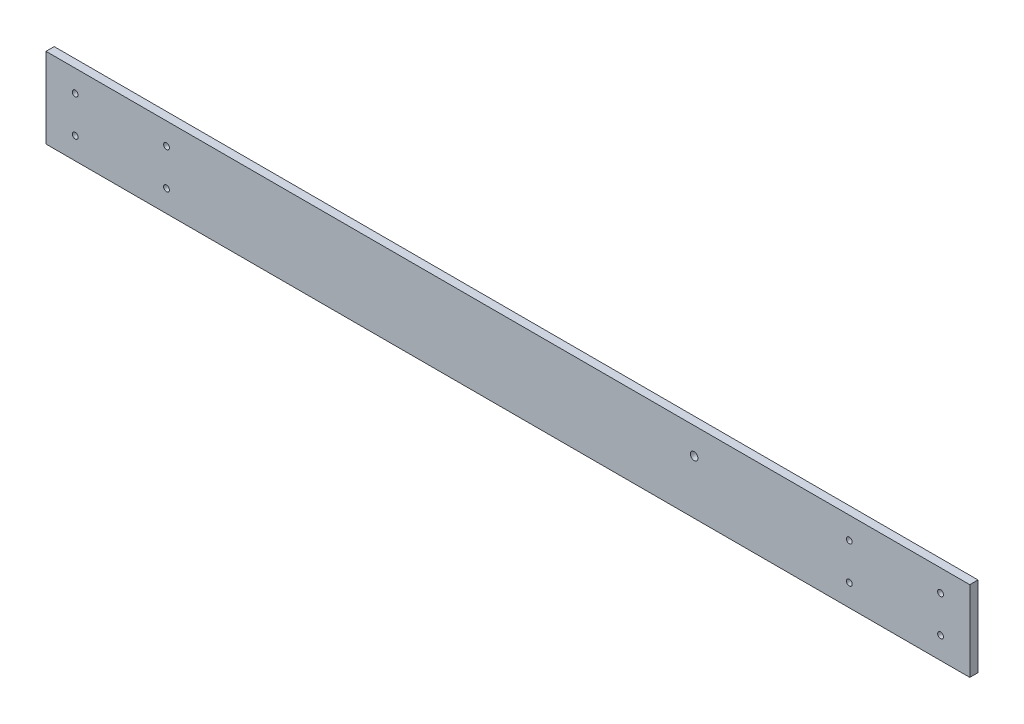
SolidWorks part; units mm, degrees
ref_plane "Front Plane" through (0, 0, 0) normal (0, 0, 1) x (1, 0, 0)
ref_plane "Top Plane" through (0, 0, 0) normal (0, 1, 0) x (1, 0, 0)
ref_plane "Right Plane" through (0, 0, 0) normal (1, 0, 0) x (0, 0, -1)
sketch "Sketch2" plane through (0, 0, 0) normal (0, 0, 1) x (1, 0, 0)
  line L0 (253, 0) -> (127, 0) construction
  line L1 (-253, -22) -> (253, -22)
  line L2 (-253, -22) -> (-253, 22)
  line L3 (-253, 22) -> (253, 22)
  line L4 (253, -22) -> (253, 22)
  line L5 (-253, -22) -> (253, 22) construction
  line L6 (-253, 22) -> (253, -22) construction
  line L7 (127, -1) -> (127, 9) construction
  line L8 (247, 3.3321) -> (247, 22) construction
  line L9 (0, 0) -> (0, 11.9613) construction
  circle A0 centre (102, 7.5) radius 2.1 construction
  circle A1 centre (102, 7.5) radius 2.1
  circle A2 centre (237, 10) radius 1.6
  circle A3 centre (187, 10) radius 1.6
  circle A6 centre (187, -10) radius 1.6
  circle A9 centre (237, -10) radius 1.6
  circle A10 centre (-187, 10) radius 1.6
  circle A11 centre (-187, -10) radius 1.6
  circle A12 centre (-237, -10) radius 1.6
  circle A13 centre (-237, 10) radius 1.6
  point P0 (0, 0)
  dimension "D3" = 10
  dimension "D5" = 3.2
  dimension "D1" = 44
  dimension "D2" = 506
  dimension "D4" = 10
  dimension "D6" = 2
  dimension "D7" = 2
extrude "Boss-Extrude1" add sketch "Sketch2" along normal blind 4.5
